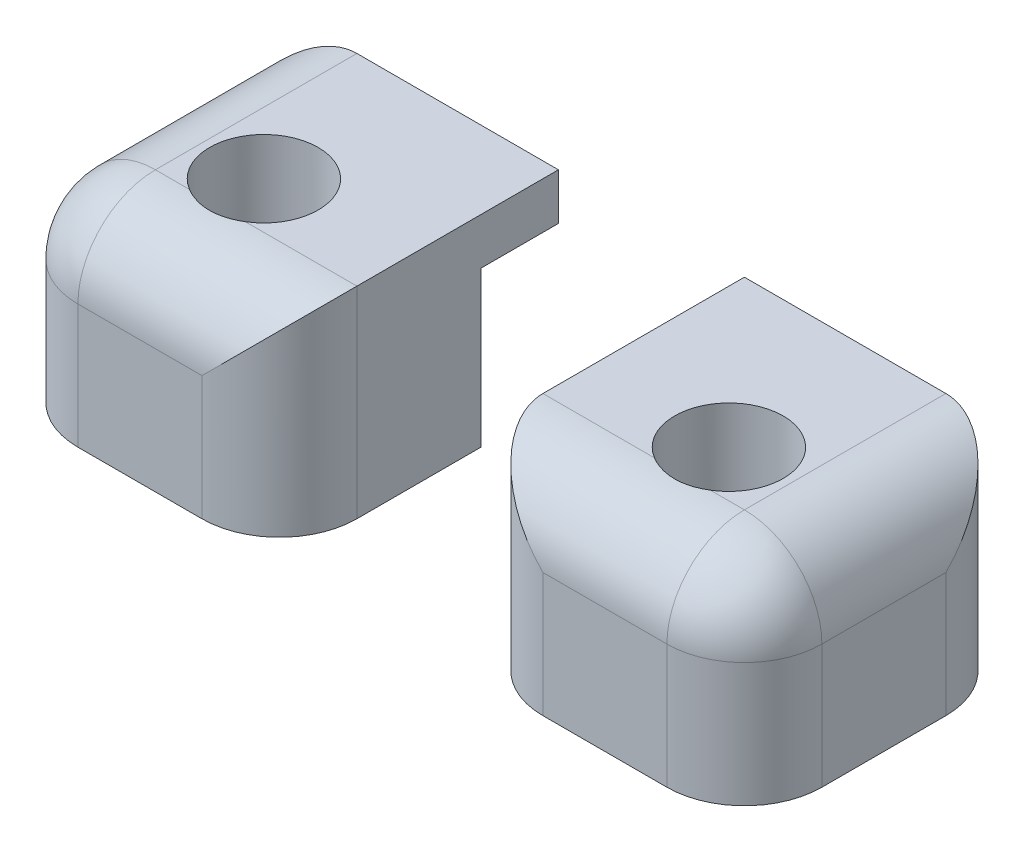
SolidWorks part; units mm, degrees
ref_plane "Front Plane" through (0, 0, 0) normal (0, 0, 1) x (1, 0, 0)
ref_plane "Top Plane" through (0, 0, 0) normal (0, 1, 0) x (1, 0, 0)
ref_plane "Right Plane" through (0, 0, 0) normal (1, 0, 0) x (0, 0, -1)
sketch "Sketch1" plane through (0, 0, 0) normal (0, 1, 0) x (1, 0, 0)
  line L1 (-9, -9) -> (9, -9)
  line L2 (-9, -9) -> (-9, 9)
  line L3 (-9, 9) -> (9, 9)
  line L4 (9, -9) -> (9, 9)
  line L5 (-9, -9) -> (9, 9) construction
  line L6 (-9, 9) -> (9, -9) construction
  line L7 (9, 9) -> (-1, 9)
  line L8 (9, 9) -> (9, 4)
  line L9 (9, 4) -> (-1, 4)
  line L10 (-1, 9) -> (-1, 4)
  point P0 (0, 0)
  dimension "D1" = 18
  dimension "D2" = 18
  dimension "D3" = 10
  dimension "D4" = 5
extrude "Boss-Extrude1" add sketch "Sketch1" along normal blind 10 contours L10 L3 L2 L1 L4 L9 region at (-0.7299, 0, 1.1861)
extrude "Boss-Extrude2" add sketch "Sketch1<3>" along normal blind 3 from offset 10 contours L3 L10 L9 L4 | L10 L3 L2 L1 L4 L9 region at (-0.7299, 0, 1.1861) region at (4, 0, -6.5)
sketch "Sketch1<3>" plane through (0, 0, 0) normal (0, 1, 0) x (1, 0, 0) same geometry as "Sketch1"
sketch "Sketch2" plane through (0, 13, 0) normal (0, 1, 0) x (1, 0, 0)
  line L0 (0, -1) -> (0, 0) construction
  circle A0 centre (0, -1) radius 3.5
  circle A1 centre (0, -1) radius 2
  dimension "D1" = 7
  dimension "D2" = 4
  dimension "D3" = 1
extrude "Cut-Extrude1" cut sketch "Sketch2" against normal blind 10
extrude "Cut-Extrude2" cut sketch "Sketch2<2>" against normal through all contours A1 region at (0, 13, 1)
sketch "Sketch2<2>" plane through (0, 13, 0) normal (0, 1, 0) x (1, 0, 0) same geometry as "Sketch2"
chamfer "Chamfer1" distance 1 angle 45 1 edges at (0, 3, 3)
fillet "Fillet1" radius 5 5 edges at (-9, 6.5, -9) (9, 6.5, 9) (-9, 6.5, 9) (0, 13, 9) (-9, 13, 0)
ref_plane "Plane1" through (15, 0, 0) normal (1, 0, 0) x (0, 0, -1)
mirror "Mirror2" about plane through (15, 0, 0) normal (1, 0, 0) of bodies 104
